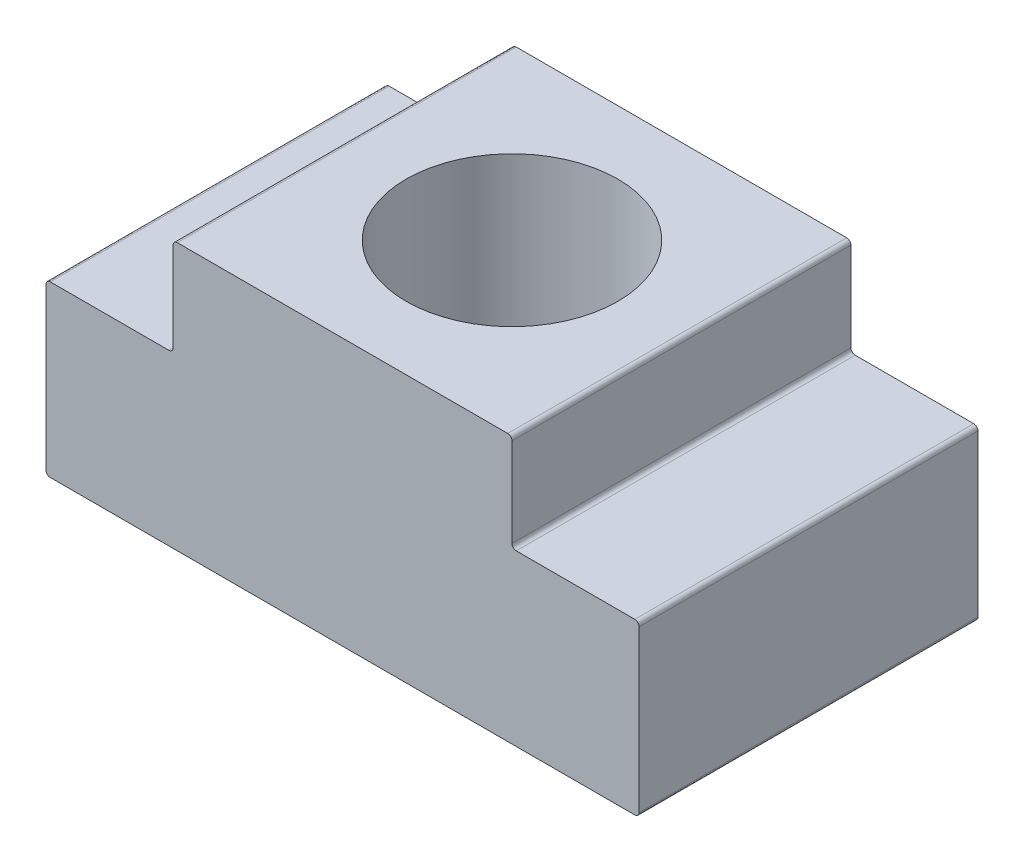
SolidWorks part; units mm, degrees
material "Chrome Stainless Steel"
ref_plane "Front Plane" through (0, 0, 0) normal (0, 0, 1) x (1, 0, 0)
ref_plane "Top Plane" through (0, 0, 0) normal (0, 1, 0) x (1, 0, 0)
ref_plane "Right Plane" through (0, 0, 0) normal (1, 0, 0) x (0, 0, -1)
sketch "Sketch1" plane through (0, 0, 0) normal (0, 0, 1) x (1, 0, 0)
  line L0 (0, 6.3) -> (4, 6.3)
  line L1 (0, -55) -> (0, 55) construction
  line L2 (4, 6.3) -> (4, 4)
  line L3 (4, 4) -> (7, 4)
  line L4 (7, 4) -> (7, 0)
  line L5 (55, 0) -> (-55, 0) construction
  line L6 (7, 0) -> (0, 0)
  line L7 (0, 0) -> (0, 6.3)
  dimension "D1" = 4
  dimension "D2" = 2.3
  dimension "D3" = 4
  dimension "D4" = 7
extrude "Boss-Extrude1" add sketch "Sketch1" along normal blind 8
mirror "Mirror1" about plane through (0, 0, 0) normal (1, 0, 0) of "Boss-Extrude1"
sketch "Sketch2" plane through (0, 6.3, 0) normal (0, 1, 0) x (1, 0, 0)
  line L0 (0, -3.465) -> (0, 3.465) construction
  line L1 (-3.465, 0) -> (3.465, 0) construction
  circle A0 centre (0, -4) radius 2.5
  dimension "D1" = 5
  dimension "D2" = 4
extrude "Cut-Extrude1" cut sketch "Sketch2" against normal blind 7
fillet "Fillet1" radius 0.1 8 edges at (4, 4, 4) (7, 0, 4) (7, 4, 4) (-4, 6.3, 4) (4, 6.3, 4) (-7, 0, 4) (-7, 4, 4) (-4, 4, 4)
